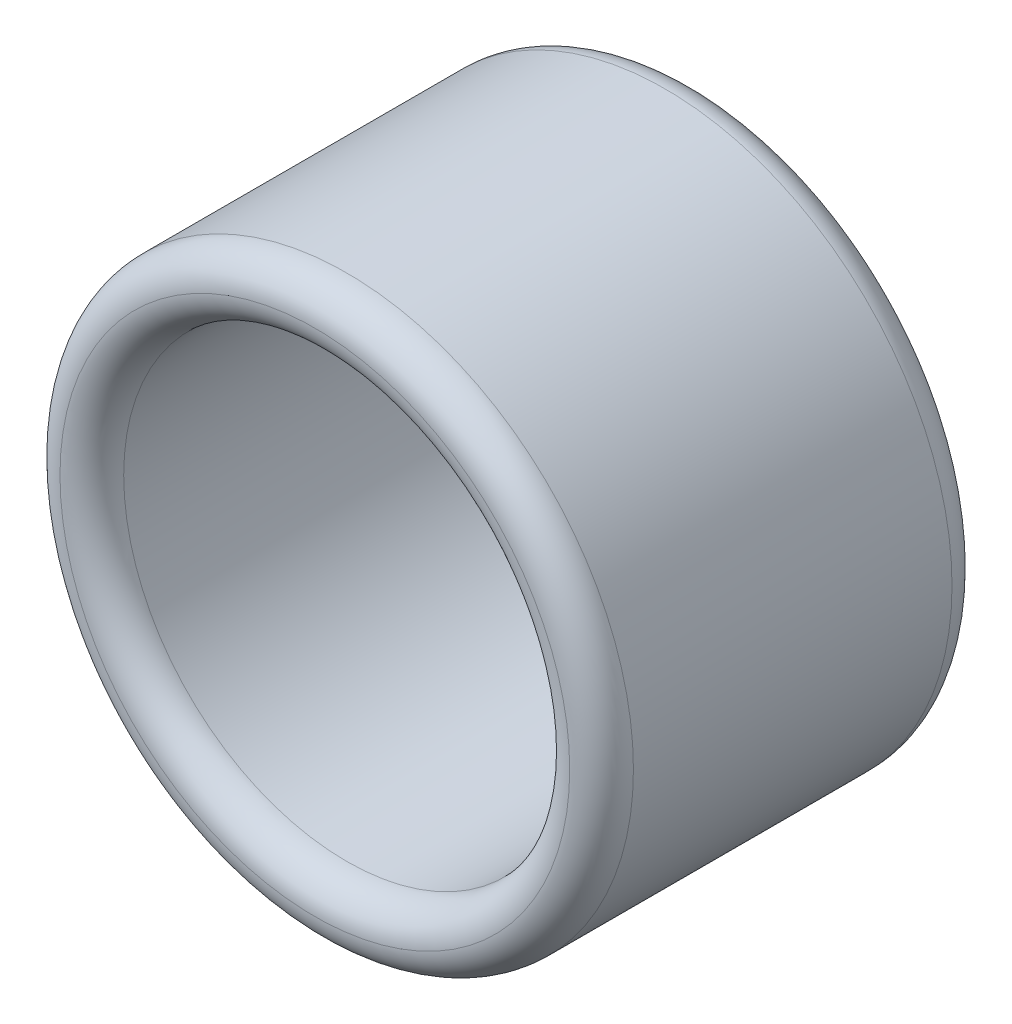
SolidWorks part; units mm, degrees
material "1023 Carbon Steel Sheet (SS)"
ref_plane "Front Plane" through (0, 0, 0) normal (0, 0, 1) x (1, 0, 0)
ref_plane "Top Plane" through (0, 0, 0) normal (0, 1, 0) x (1, 0, 0)
ref_plane "Right Plane" through (0, 0, 0) normal (1, 0, 0) x (0, 0, -1)
sketch "Sketch1" plane through (0, 0, 0) normal (0, 0, 1) x (1, 0, 0)
  circle A0 centre (-54.9063, 0) radius 4.5
  circle A1 centre (-54.9063, 0) radius 3.5
  dimension "D1" = 9
  dimension "D2" = 7
extrude "Boss-Extrude1" add sketch "Sketch1" along normal blind 6
fillet "Fillet1" radius 0.5 4 edges at (-51.4063, 0, 0) (-50.4063, 0, 0) (-51.4063, 0, 6) (-50.4063, 0, 6)
